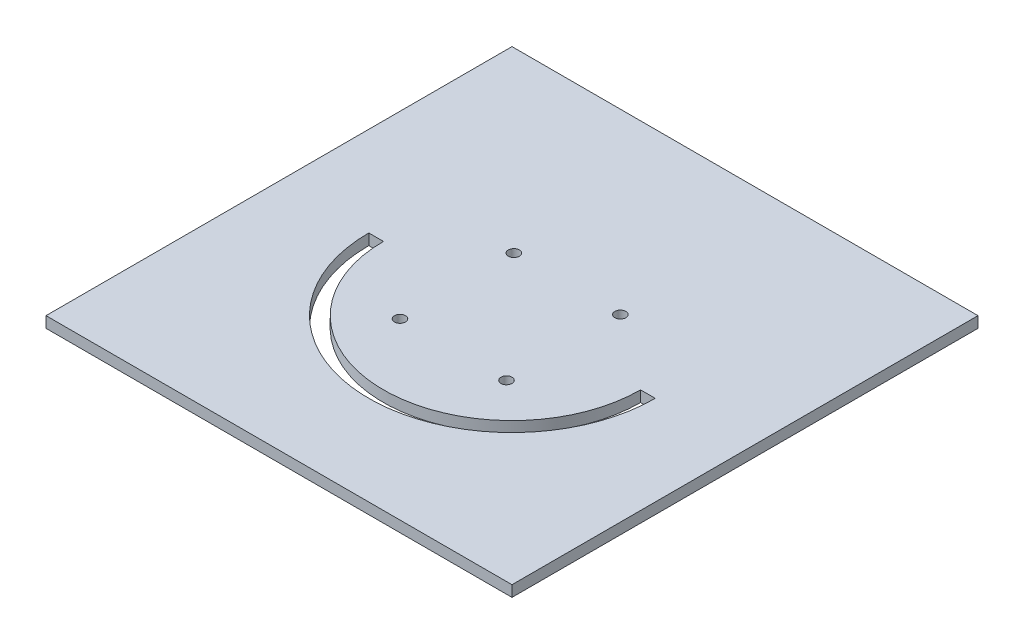
SolidWorks part; units mm, degrees
ref_plane "Front Plane" through (0, 0, 0) normal (0, 0, 1) x (1, 0, 0)
ref_plane "Top Plane" through (0, 0, 0) normal (0, 1, 0) x (1, 0, 0)
ref_plane "Right Plane" through (0, 0, 0) normal (1, 0, 0) x (0, 0, -1)
sketch "Sketch2" plane through (0, 0, 0) normal (0, 1, 0) x (1, 0, 0)
  line L1 (63.4385, 63.4385) -> (63.4385, -63.4385)
  line L2 (63.4385, -63.4385) -> (-63.4385, -63.4385)
  line L3 (-63.4385, -63.4385) -> (-63.4385, 63.4385)
  line L4 (-63.4385, 63.4385) -> (63.4385, 63.4385)
  circle A0 centre (14.5, 15) radius 1.5
  circle A1 centre (-14.5, 15) radius 1.5
  circle A2 centre (-14.5, -16) radius 1.5
  circle A3 centre (14.5, -16) radius 1.5
extrude "Boss-Extrude1" add sketch "Sketch2" along normal blind 3
sketch "Sketch3" plane through (0, 3, 0) normal (0, 1, 0) x (1, 0, 0)
  line L0 (-39, 0) -> (-35, 0) construction
  line L1 (-39, 0) -> (-35, 0)
  line L2 (35, 0) -> (39, 0)
  line L3 (35, 0) -> (39, 0) construction
  arc A0 (-35, 0) -> (35, 0) centre (0, 0) ccw
  arc A1 (-39, 0) -> (39, 0) centre (0, 0) ccw
  dimension "D1" = 70
  dimension "D2" = 4
extrude "Cut-Extrude1" cut sketch "Sketch3" against normal blind 10
